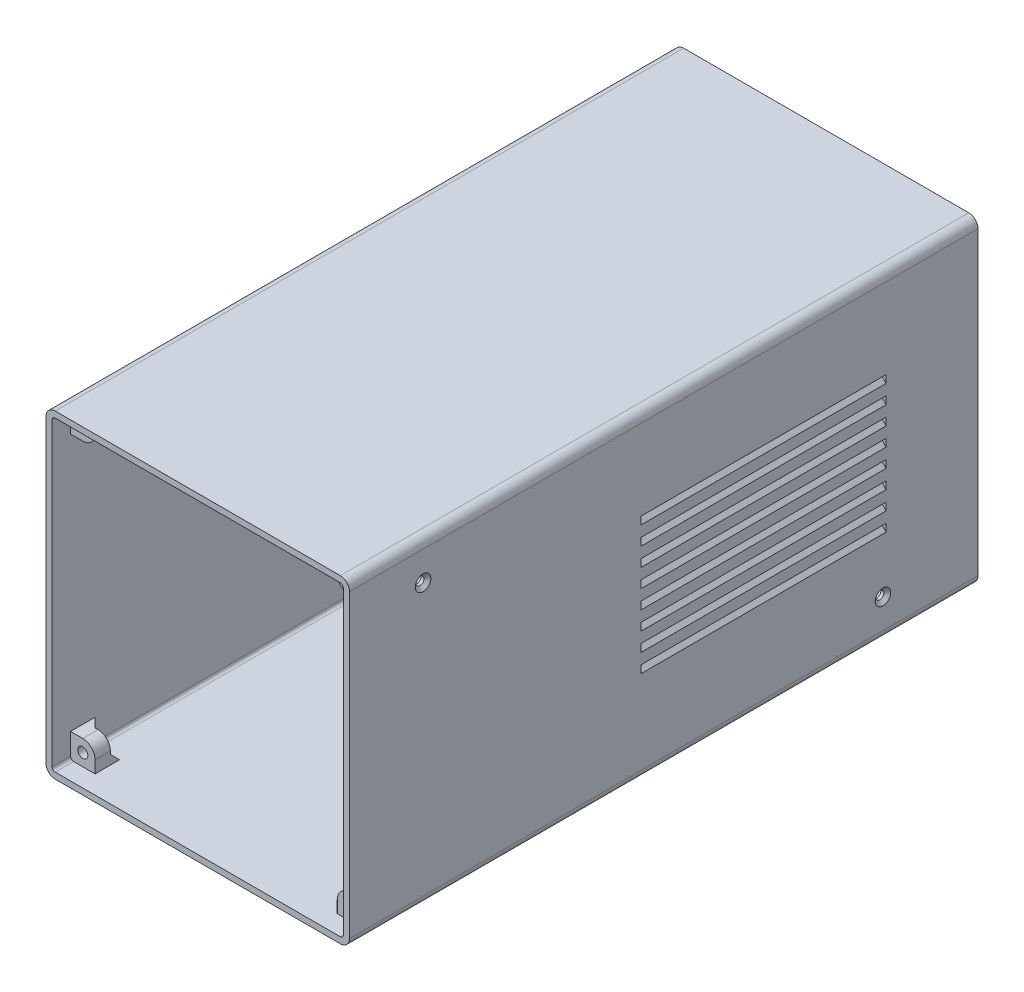
SolidWorks part; units mm, degrees
ref_plane "前视基准面" through (0, 0, 0) normal (0, 0, 1) x (1, 0, 0)
ref_plane "上视基准面" through (0, 0, 0) normal (0, 1, 0) x (1, 0, 0)
ref_plane "右视基准面" through (0, 0, 0) normal (1, 0, 0) x (0, 0, -1)
sketch "草图1" plane through (0, 0, 0) normal (0, 0, 1) x (1, 0, 0)
  line L1 (-46.5, -50) -> (46.5, -50)
  line L2 (-47.5, -49) -> (-47.5, 49)
  line L3 (-46.5, 50) -> (46.5, 50)
  line L4 (47.5, -49) -> (47.5, 49)
  line L5 (-47.5, -50) -> (47.5, 50) construction
  line L6 (-47.5, 50) -> (47.5, -50) construction
  arc A0 (-46.5, -50) -> (-47.5, -49) centre (-46.5, -49) cw
  arc A1 (46.5, -50) -> (47.5, -49) centre (46.5, -49) ccw
  arc A2 (46.5, 50) -> (47.5, 49) centre (46.5, 49) cw
  arc A3 (-47.5, 49) -> (-46.5, 50) centre (-46.5, 49) cw
  point P0 (0, 0)
  dimension "D3" = 1
  dimension "D1" = 100
  dimension "D2" = 95
extrude "凸台-拉伸1" add sketch "草图1" along normal blind 205
shell "抽壳1" thickness 2 removed face at (0, 0, 205) removed face at (0, 0, 0) outward yes
ref_plane "基准面1" through (0, 0, 30) normal (0, 0, 1) x (1, 0, 0)
ref_plane "基准面2" through (0, 0, 6) normal (0, 0, -1) x (-1, 0, 0)
ref_plane "基准面3" through (0, 0, 199) normal (0, 0, 1) x (1, 0, 0)
sketch "草图6" plane through (0, 0, 6) normal (0, 0, -1) x (-1, 0, 0)
  line L0 (0, 0) -> (0, 33.2854) construction
  line L1 (-43.5, 42) -> (-47.5, 42)
  line L2 (-39.5, 46) -> (-39.5, 50)
  line L3 (-39.5, 50) -> (-47.5, 50)
  line L4 (-47.5, 42) -> (-47.5, 50)
  line L5 (0, 0) -> (27.226, 0) construction
  line L6 (-46.5, 50) -> (46.5, 50) construction
  line L7 (-47.5, -49) -> (-47.5, 49) construction
  line L8 (39.5, 46) -> (39.5, 50)
  line L9 (43.5, 42) -> (47.5, 42)
  line L10 (47.5, 42) -> (47.5, 50)
  line L11 (39.5, 50) -> (47.5, 50)
  line L12 (39.5, -50) -> (47.5, -50)
  line L13 (47.5, -42) -> (47.5, -50)
  line L14 (43.5, -42) -> (47.5, -42)
  line L15 (39.5, -46) -> (39.5, -50)
  line L16 (-47.5, -42) -> (-47.5, -50)
  line L17 (-39.5, -50) -> (-47.5, -50)
  line L18 (-39.5, -46) -> (-39.5, -50)
  line L19 (-43.5, -42) -> (-47.5, -42)
  arc A0 (-43.5, 42) -> (-39.5, 46) centre (-43.5, 46) ccw
  circle A1 centre (-43.5, 46) radius 1.65
  circle A2 centre (43.5, 46) radius 1.65
  arc A3 (43.5, 42) -> (39.5, 46) centre (43.5, 46) cw
  arc A4 (43.5, -42) -> (39.5, -46) centre (43.5, -46) ccw
  circle A5 centre (43.5, -46) radius 1.65
  circle A6 centre (-43.5, -46) radius 1.65
  arc A7 (-43.5, -42) -> (-39.5, -46) centre (-43.5, -46) cw
  point P15 (-39.5, 42)
  dimension "D3" = 4
  dimension "D4" = 3.3
  dimension "D1" = 8
  dimension "D2" = 8
extrude "凸台-拉伸2" add sketch "草图6" against normal blind 5
sketch "草图7" plane through (0, 0, 199) normal (0, 0, 1) x (1, 0, 0)
  line L0 (-46.5, -50) -> (-39.5, -50) construction
  line L1 (-39.5, -50) -> (-39.5, -46) construction
  line L2 (-43.5, -42) -> (-47.5, -42) construction
  line L3 (-47.5, -42) -> (-47.5, -49) construction
  line L4 (39.5, -50) -> (46.5, -50) construction
  line L5 (47.5, -49) -> (47.5, -42) construction
  line L6 (47.5, -42) -> (43.5, -42) construction
  line L7 (39.5, -46) -> (39.5, -50) construction
  line L8 (46.5, 50) -> (39.5, 50) construction
  line L9 (39.5, 50) -> (39.5, 46) construction
  line L10 (43.5, 42) -> (47.5, 42) construction
  line L11 (47.5, 42) -> (47.5, 49) construction
  line L12 (-39.5, 50) -> (-46.5, 50) construction
  line L13 (-47.5, 49) -> (-47.5, 42) construction
  line L14 (-47.5, 42) -> (-43.5, 42) construction
  line L15 (-39.5, 46) -> (-39.5, 50) construction
  line L16 (-46.5, -50) -> (-39.5, -50)
  line L17 (-39.5, -50) -> (-39.5, -46)
  line L18 (-43.5, -42) -> (-47.5, -42)
  line L19 (-47.5, -42) -> (-47.5, -49)
  line L20 (39.5, -50) -> (46.5, -50)
  line L21 (47.5, -49) -> (47.5, -42)
  line L22 (47.5, -42) -> (43.5, -42)
  line L23 (39.5, -46) -> (39.5, -50)
  line L24 (46.5, 50) -> (39.5, 50)
  line L25 (39.5, 50) -> (39.5, 46)
  line L26 (43.5, 42) -> (47.5, 42)
  line L27 (47.5, 42) -> (47.5, 49)
  line L28 (-39.5, 50) -> (-46.5, 50)
  line L29 (-47.5, 49) -> (-47.5, 42)
  line L30 (-47.5, 42) -> (-43.5, 42)
  line L31 (-39.5, 46) -> (-39.5, 50)
  arc A0 (-47.5, -49) -> (-46.5, -50) centre (-46.5, -49) ccw construction
  arc A1 (-39.5, -46) -> (-43.5, -42) centre (-43.5, -46) ccw construction
  arc A2 (46.5, -50) -> (47.5, -49) centre (46.5, -49) ccw construction
  arc A3 (43.5, -42) -> (39.5, -46) centre (43.5, -46) ccw construction
  arc A4 (47.5, 49) -> (46.5, 50) centre (46.5, 49) ccw construction
  arc A5 (39.5, 46) -> (43.5, 42) centre (43.5, 46) ccw construction
  arc A6 (-46.5, 50) -> (-47.5, 49) centre (-46.5, 49) ccw construction
  arc A7 (-43.5, 42) -> (-39.5, 46) centre (-43.5, 46) ccw construction
  circle A8 centre (43.5, -46) radius 1.65 construction
  circle A9 centre (43.5, 46) radius 1.65 construction
  circle A10 centre (-43.5, 46) radius 1.65 construction
  circle A11 centre (-43.5, -46) radius 1.65 construction
  arc A12 (-47.5, -49) -> (-46.5, -50) centre (-46.5, -49) ccw
  arc A13 (-39.5, -46) -> (-43.5, -42) centre (-43.5, -46) ccw
  arc A14 (46.5, -50) -> (47.5, -49) centre (46.5, -49) ccw
  arc A15 (43.5, -42) -> (39.5, -46) centre (43.5, -46) ccw
  arc A16 (47.5, 49) -> (46.5, 50) centre (46.5, 49) ccw
  arc A17 (39.5, 46) -> (43.5, 42) centre (43.5, 46) ccw
  arc A18 (-46.5, 50) -> (-47.5, 49) centre (-46.5, 49) ccw
  arc A19 (-43.5, 42) -> (-39.5, 46) centre (-43.5, 46) ccw
  circle A20 centre (43.5, -46) radius 1.65
  circle A21 centre (43.5, 46) radius 1.65
  circle A22 centre (-43.5, 46) radius 1.65
  circle A23 centre (-43.5, -46) radius 1.65
extrude "凸台-拉伸3" add sketch "草图7" against normal blind 5
sketch "草图8" plane through (-49.5, 0, 0) normal (-1, 0, 0) x (0, 0, 1)
  line L0 (0, 49) -> (0, -49) construction
  line L1 (96, -43) -> (32, -43) construction
  line L2 (96, -43) -> (96, 43) construction
  line L3 (96, 43) -> (32, 43) construction
  line L4 (32, -43) -> (32, 43) construction
  line L5 (96, -43) -> (32, 43) construction
  line L6 (96, 43) -> (32, -43) construction
  line L7 (100, -46.5) -> (28, -46.5) construction
  line L8 (100, -46.5) -> (100, 46.5) construction
  line L9 (100, 46.5) -> (28, 46.5) construction
  line L10 (28, -46.5) -> (28, 46.5) construction
  line L11 (100, -46.5) -> (28, 46.5) construction
  line L12 (100, 46.5) -> (28, -46.5) construction
  point P0 (64, 0)
  point P5 (64, 0)
  dimension "D1" = 72
  dimension "D2" = 93
  dimension "D3" = 86
  dimension "D4" = 64
  dimension "D5" = 28
hole_wizard "#3 平头机械螺钉的锥形沉头孔 (100)1" positions "草图9" profile "草图10" countersink size "#3" standard "ANSI Inch" end condition up to next
sketch "草图9" plane through (-49.5, 0, 0) normal (-1, 0, 0) x (0, 0, 1)
  point P0 (32, 43)
  point P3 (96, 43)
  point P6 (96, -43)
  point P9 (32, -43)
sketch "草图10" plane through (-49.5, 43, 32) normal (0, 1, 0) x (0, 0, 1)
  line L0 (0, 0) -> (0, 2)
  line L1 (0, 2) -> (1.3208, 2)
  line L2 (1.3208, 2) -> (1.3208, 1.0124)
  line L3 (1.3208, 1.0124) -> (2.5273, 0)
  line L5 (2.5273, 0) -> (0, 0)
  line L6 (-1.3208, 1.0124) -> (-2.5273, 0) construction
  line L11 (0, -6.35) -> (0, 107.95) construction
  dimension "通孔孔直径" = 2.6416
  dimension "通孔孔深度" = 2
  dimension "近端锥形沉头孔直径" = 5.0546
  dimension "近端锥形沉头孔角度" = 100
sketch "草图11" plane through (49.5, 0, 0) normal (1, 0, 0) x (0, 0, -1)
  line L0 (0, -49) -> (0, 49) construction
  line L1 (-26, -47.5) -> (-186, -47.5) construction
  line L2 (-26, -47.5) -> (-26, 47.5) construction
  line L3 (-26, 47.5) -> (-186, 47.5) construction
  line L4 (-186, -47.5) -> (-186, 47.5) construction
  line L5 (-26, -47.5) -> (-186, 47.5) construction
  line L6 (-26, 47.5) -> (-186, -47.5) construction
  line L7 (-186, 39.5) -> (-181, 39.5) construction
  line L8 (-26, -39.5) -> (-31, -39.5) construction
  point P0 (-106, 0)
  dimension "D1" = 160
  dimension "D2" = 95
  dimension "D3" = 26
  dimension "D4" = 5
  dimension "D5" = 5
  dimension "D6" = 8
  dimension "D7" = 8
hole_wizard "#3 平头机械螺钉的锥形沉头孔 (100)2" positions "草图12" profile "草图13" countersink size "#3" standard "ANSI Inch" end condition up to next
sketch "草图12" plane through (49.5, 0, 0) normal (1, 0, 0) x (0, 0, -1)
  point P0 (-181, 39.5)
  point P3 (-31, -39.5)
sketch "草图13" plane through (49.5, 39.5, 181) normal (0, 1, 0) x (0, 0, -1)
  line L0 (0, 0) -> (0, 2)
  line L1 (0, 2) -> (1.3208, 2)
  line L2 (1.3208, 2) -> (1.3208, 1.0124)
  line L3 (1.3208, 1.0124) -> (2.5273, 0)
  line L5 (2.5273, 0) -> (0, 0)
  line L6 (-1.3208, 1.0124) -> (-2.5273, 0) construction
  line L11 (0, -6.35) -> (0, 107.95) construction
  dimension "通孔孔直径" = 2.6416
  dimension "通孔孔深度" = 2
  dimension "近端锥形沉头孔直径" = 5.0546
  dimension "近端锥形沉头孔角度" = 100
sketch "草图2" plane through (0, 0, 30) normal (0, 0, 1) x (1, 0, 0)
  line L0 (0, 0) -> (0, 60.9493) construction
  line L1 (49.5, 20.2788) -> (47.5, 22.5)
  line L2 (49.5, 20.2788) -> (49.5, 22.7788)
  line L3 (47.5, 22.5) -> (47.5, 25)
  line L4 (49.5, 22.7788) -> (47.5, 25)
  line L5 (49.5, -49) -> (49.5, 49) construction
  line L6 (47.5, -49) -> (47.5, 49) construction
  line L7 (46.5, 50) -> (-46.5, 50) construction
  line L8 (49.5, 16.7788) -> (47.5, 19)
  line L9 (47.5, 16.5) -> (47.5, 19)
  line L10 (49.5, 14.2788) -> (49.5, 16.7788)
  line L11 (49.5, 14.2788) -> (47.5, 16.5)
  line L12 (49.5, 10.7788) -> (47.5, 13)
  line L13 (47.5, 10.5) -> (47.5, 13)
  line L14 (49.5, 8.2788) -> (49.5, 10.7788)
  line L15 (49.5, 8.2788) -> (47.5, 10.5)
  line L16 (49.5, 4.7788) -> (47.5, 7)
  line L17 (47.5, 4.5) -> (47.5, 7)
  line L18 (49.5, 2.2788) -> (49.5, 4.7788)
  line L19 (49.5, 2.2788) -> (47.5, 4.5)
  line L20 (49.5, -1.2212) -> (47.5, 1)
  line L21 (47.5, -1.5) -> (47.5, 1)
  line L22 (49.5, -3.7212) -> (49.5, -1.2212)
  line L23 (49.5, -3.7212) -> (47.5, -1.5)
  line L24 (49.5, -7.2212) -> (47.5, -5)
  line L25 (47.5, -7.5) -> (47.5, -5)
  line L26 (49.5, -9.7212) -> (49.5, -7.2212)
  line L27 (49.5, -9.7212) -> (47.5, -7.5)
  line L28 (49.5, -13.2212) -> (47.5, -11)
  line L29 (47.5, -13.5) -> (47.5, -11)
  line L30 (49.5, -15.7212) -> (49.5, -13.2212)
  line L31 (49.5, -15.7212) -> (47.5, -13.5)
  line L32 (49.5, -19.2212) -> (47.5, -17)
  line L33 (47.5, -19.5) -> (47.5, -17)
  line L34 (49.5, -21.7212) -> (49.5, -19.2212)
  line L35 (49.5, -21.7212) -> (47.5, -19.5)
  line L52 (-49.5, -21.7212) -> (-47.5, -19.5)
  line L53 (-49.5, -21.7212) -> (-49.5, -19.2212)
  line L54 (-47.5, -19.5) -> (-47.5, -17)
  line L55 (-49.5, -19.2212) -> (-47.5, -17)
  line L56 (-49.5, -15.7212) -> (-47.5, -13.5)
  line L57 (-49.5, -15.7212) -> (-49.5, -13.2212)
  line L58 (-47.5, -13.5) -> (-47.5, -11)
  line L59 (-49.5, -13.2212) -> (-47.5, -11)
  line L60 (-49.5, -9.7212) -> (-47.5, -7.5)
  line L61 (-49.5, -9.7212) -> (-49.5, -7.2212)
  line L62 (-47.5, -7.5) -> (-47.5, -5)
  line L63 (-49.5, -7.2212) -> (-47.5, -5)
  line L64 (-49.5, -3.7212) -> (-47.5, -1.5)
  line L65 (-49.5, -3.7212) -> (-49.5, -1.2212)
  line L66 (-47.5, -1.5) -> (-47.5, 1)
  line L67 (-49.5, -1.2212) -> (-47.5, 1)
  line L68 (-49.5, 2.2788) -> (-47.5, 4.5)
  line L69 (-49.5, 2.2788) -> (-49.5, 4.7788)
  line L70 (-47.5, 4.5) -> (-47.5, 7)
  line L71 (-49.5, 4.7788) -> (-47.5, 7)
  line L72 (-49.5, 8.2788) -> (-47.5, 10.5)
  line L73 (-49.5, 8.2788) -> (-49.5, 10.7788)
  line L74 (-47.5, 10.5) -> (-47.5, 13)
  line L75 (-49.5, 10.7788) -> (-47.5, 13)
  line L76 (-49.5, 14.2788) -> (-47.5, 16.5)
  line L77 (-49.5, 14.2788) -> (-49.5, 16.7788)
  line L78 (-47.5, 16.5) -> (-47.5, 19)
  line L79 (-49.5, 16.7788) -> (-47.5, 19)
  line L80 (-49.5, 22.7788) -> (-47.5, 25)
  line L81 (-47.5, 22.5) -> (-47.5, 25)
  line L82 (-49.5, 20.2788) -> (-49.5, 22.7788)
  line L83 (-49.5, 20.2788) -> (-47.5, 22.5)
  dimension "D1" = 42
  dimension "D2" = 2.5
  dimension "D3" = 25
  dimension "D4" = 8
extrude "切除-拉伸1" cut sketch "草图2" along normal blind 80
chamfer "倒角1" distance 3 angle 45 16 edges at (-43, -50, 194) (-47.5, -45.5, 194) (43, -50, 194) (47.5, -45.5, 194) (43, 50, 194) (47.5, 45.5, 194) (-43, 50, 194) (-47.5, 45.5, 194) (47.5, 45.5, 11) (43, 50, 11) (-47.5, 45.5, 11) (-43, 50, 11) (-43, -50, 11) (-47.5, -45.5, 11) (43, -50, 11) (47.5, -45.5, 11) tangent propagation no
sketch "草图14" plane through (0, 0, 11) normal (0, 0, 1) x (1, 0, 0)
  line L1 (-43.5, 49.1754) -> (-46.25, 47.5877)
  line L2 (-46.25, 47.5877) -> (-46.25, 44.4123)
  line L3 (-46.25, 44.4123) -> (-43.5, 42.8246)
  line L4 (-43.5, 42.8246) -> (-40.75, 44.4123)
  line L5 (-40.75, 44.4123) -> (-40.75, 47.5877)
  line L6 (-40.75, 47.5877) -> (-43.5, 49.1754)
  line L7 (43.5, 49.1754) -> (40.75, 47.5877)
  line L8 (40.75, 47.5877) -> (40.75, 44.4123)
  line L9 (40.75, 44.4123) -> (43.5, 42.8246)
  line L10 (43.5, 42.8246) -> (46.25, 44.4123)
  line L11 (46.25, 44.4123) -> (46.25, 47.5877)
  line L12 (46.25, 47.5877) -> (43.5, 49.1754)
  line L13 (43.5, -42.8246) -> (40.75, -44.4123)
  line L14 (40.75, -44.4123) -> (40.75, -47.5877)
  line L15 (40.75, -47.5877) -> (43.5, -49.1754)
  line L16 (43.5, -49.1754) -> (46.25, -47.5877)
  line L17 (46.25, -47.5877) -> (46.25, -44.4123)
  line L18 (46.25, -44.4123) -> (43.5, -42.8246)
  line L19 (-43.5, -42.8246) -> (-46.25, -44.4123)
  line L20 (-46.25, -44.4123) -> (-46.25, -47.5877)
  line L21 (-46.25, -47.5877) -> (-43.5, -49.1754)
  line L22 (-43.5, -49.1754) -> (-40.75, -47.5877)
  line L23 (-40.75, -47.5877) -> (-40.75, -44.4123)
  line L24 (-40.75, -44.4123) -> (-43.5, -42.8246)
  circle A0 centre (-43.5, 46) radius 2.75 construction
  circle A1 centre (43.5, 46) radius 2.75 construction
  circle A2 centre (43.5, -46) radius 2.75 construction
  circle A3 centre (-43.5, -46) radius 2.75 construction
  dimension "D1" = 5.5
extrude "切除-拉伸2" cut sketch "草图14" along normal blind 10 and the other way blind 2
sketch "草图15" plane through (0, 0, 194) normal (0, 0, 1) x (1, 0, 0)
  line L1 (-43.5, 49.1754) -> (-46.25, 47.5877)
  line L2 (-46.25, 47.5877) -> (-46.25, 44.4123)
  line L3 (-46.25, 44.4123) -> (-43.5, 42.8246)
  line L4 (-43.5, 42.8246) -> (-40.75, 44.4123)
  line L5 (-40.75, 44.4123) -> (-40.75, 47.5877)
  line L6 (-40.75, 47.5877) -> (-43.5, 49.1754)
  line L7 (43.5, 49.1754) -> (40.75, 47.5877)
  line L8 (40.75, 47.5877) -> (40.75, 44.4123)
  line L9 (40.75, 44.4123) -> (43.5, 42.8246)
  line L10 (43.5, 42.8246) -> (46.25, 44.4123)
  line L11 (46.25, 44.4123) -> (46.25, 47.5877)
  line L12 (46.25, 47.5877) -> (43.5, 49.1754)
  line L13 (43.5, -42.8246) -> (40.75, -44.4123)
  line L14 (40.75, -44.4123) -> (40.75, -47.5877)
  line L15 (40.75, -47.5877) -> (43.5, -49.1754)
  line L16 (43.5, -49.1754) -> (46.25, -47.5877)
  line L17 (46.25, -47.5877) -> (46.25, -44.4123)
  line L18 (46.25, -44.4123) -> (43.5, -42.8246)
  line L19 (-43.5, -42.8246) -> (-46.25, -44.4123)
  line L20 (-46.25, -44.4123) -> (-46.25, -47.5877)
  line L21 (-46.25, -47.5877) -> (-43.5, -49.1754)
  line L22 (-43.5, -49.1754) -> (-40.75, -47.5877)
  line L23 (-40.75, -47.5877) -> (-40.75, -44.4123)
  line L24 (-40.75, -44.4123) -> (-43.5, -42.8246)
  circle A0 centre (-43.5, 46) radius 2.75 construction
  circle A1 centre (43.5, 46) radius 2.75 construction
  circle A2 centre (43.5, -46) radius 2.75 construction
  circle A3 centre (-43.5, -46) radius 2.75 construction
  dimension "D1" = 5.5
extrude "切除-拉伸3" cut sketch "草图15" against normal blind 10 and the other way blind 2
